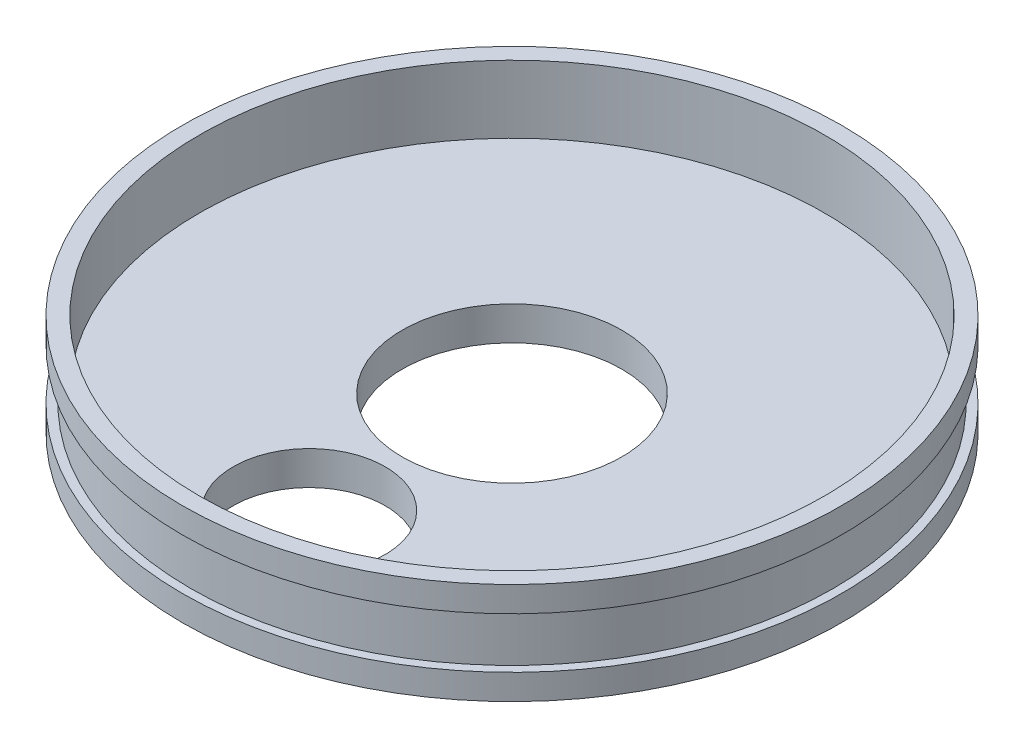
SolidWorks part; units mm, degrees
ref_plane "Front Plane" through (0, 0, 0) normal (0, 0, 1) x (1, 0, 0)
ref_plane "Top Plane" through (0, 0, 0) normal (0, 1, 0) x (1, 0, 0)
ref_plane "Right Plane" through (0, 0, 0) normal (1, 0, 0) x (0, 0, -1)
sketch "Sketch2" plane through (0, 0, 0) normal (0, 1, 0) x (1, 0, 0)
  line L0 (0, 0) -> (0, -12) construction
  circle A0 centre (0, 0) radius 18.5
  circle A1 centre (0, 0) radius 19.5
  circle A2 centre (0, 0) radius 17.5 construction
  circle A3 centre (0, -12) radius 4.5
  circle A4 centre (0, 0) radius 6.5
  dimension "D1" = 37
  dimension "D2" = 39
  dimension "D3" = 35
  dimension "D5" = 9
  dimension "D6" = 13
  dimension "D4" = 12
extrude "LidBase" add sketch "Sketch2" along normal blind 2 contours A1 A0 | A0 A3 region at (-17.9767, 0, 0) region at (-18.9485, 0, 0)
extrude "LidWalls" add sketch "Sketch2<4>" along normal blind 6 contours A1 A0 region at (-18.9485, 0, 0)
sketch "Sketch2<4>" plane through (0, 0, 0) normal (0, 1, 0) x (1, 0, 0) same geometry as "Sketch2"
sketch "Sketch3" plane through (0, 0, 0) normal (1, 0, 0) x (0, 0, -1)
  line L0 (0, 0) -> (0, 6) construction
  line L1 (19, 4.5) -> (19.5, 4.5)
  line L2 (18.5, 6) -> (-18.5, 6) construction
  line L3 (0, 0) -> (19.5, 0) construction
  line L4 (19.5, 0) -> (19.5, 1.5) construction
  line L5 (19.5, 1.5) -> (19, 1.5)
  line L6 (19, 1.5) -> (19, 4.5)
  line L7 (19.5, 4.5) -> (19.5, 1.5)
  line L9 (19.5, 0) -> (19.5, 6) construction
  line L11 (19.5, 6) -> (0, 6) construction
  dimension "D1" = 6
  dimension "D2" = 1.5
  dimension "D3" = 0.5
  dimension "D4" = 3
revolve "Beltgrooves" cut sketch "Sketch3" angle 360 about L0
